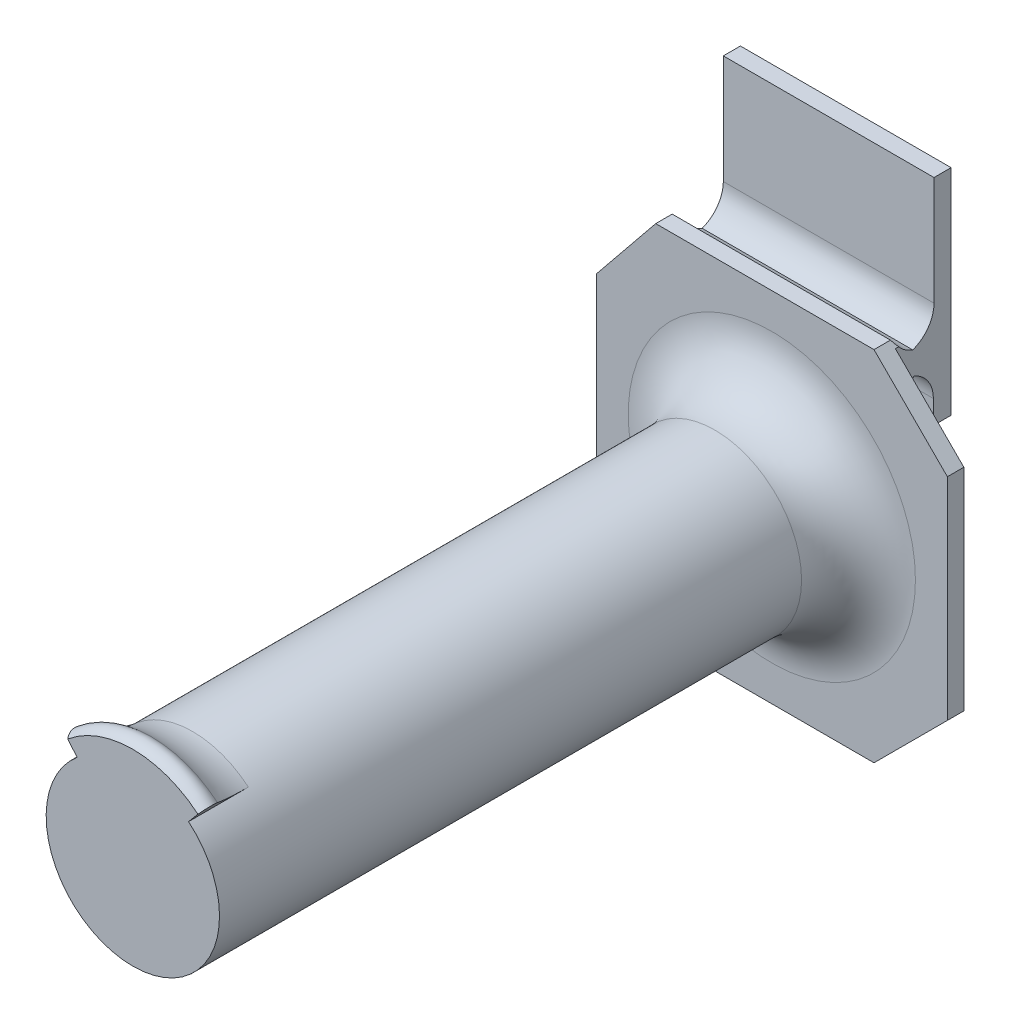
SolidWorks part; units mm, degrees
ref_plane "Front Plane" through (0, 0, 0) normal (0, 0, 1) x (1, 0, 0)
ref_plane "Top Plane" through (0, 0, 0) normal (0, 1, 0) x (1, 0, 0)
ref_plane "Right Plane" through (0, 0, 0) normal (1, 0, 0) x (0, 0, -1)
sketch "Sketch1" plane through (0, 0, 0) normal (0, 0, 1) x (1, 0, 0)
  circle A0 centre (0, 0) radius 13.7
extrude "Boss-Extrude1" add sketch "Sketch1" along normal blind 101
sketch "Sketch5" plane through (0, 0, 0) normal (0, 0, -1) x (-1, 0, 0)
  line L1 (27.75, 28.2807) -> (-27.75, 28.2807)
  line L2 (27.75, 28.2807) -> (27.75, -28.2807)
  line L3 (27.75, -28.2807) -> (-27.75, -28.2807)
  line L4 (-27.75, 28.2807) -> (-27.75, -28.2807)
  line L5 (27.75, 28.2807) -> (-27.75, -28.2807) construction
  line L6 (27.75, -28.2807) -> (-27.75, 28.2807) construction
  point P0 (0, 0)
extrude "Boss-Extrude2" add sketch "Sketch5" along normal blind 2.6 contours L1 L4 L3 L2
sketch "Sketch6" plane through (0, 0, -2.6) normal (0, 0, -1) x (-1, 0, 0)
  line L0 (-27.75, 16.6807) -> (-27.75, 28.2807)
  line L2 (27.75, 28.2807) -> (-27.75, 28.2807) construction
  line L3 (-16.15, 28.2807) -> (18.35, 28.2807) construction
  line L4 (-27.75, 0) -> (27.75, 0) construction
  line L5 (-27.75, 28.2807) -> (-27.75, -28.2807) construction
  line L6 (27.75, 28.2807) -> (27.75, -28.2807) construction
  line L7 (-16.15, -28.2807) -> (18.35, -28.2807)
  line L8 (-16.15, -28.2807) -> (-27.75, -16.6807)
  line L9 (-16.15, 28.2807) -> (-27.75, 16.6807)
  line L10 (1.1, -28.2807) -> (1.1, 28.2807) construction
  line L11 (18.35, -28.2807) -> (27.75, -18.8807)
  line L12 (27.75, -18.8807) -> (27.75, 16.6807)
  line L13 (27.75, 16.6807) -> (18.35, 28.2807)
  line L14 (-27.75, 16.6807) -> (-27.75, -16.6807) construction
  line L15 (-27.75, 28.2807) -> (-16.15, 28.2807)
  line L17 (18.35, 28.2807) -> (27.75, 28.2807)
  line L18 (27.75, 28.2807) -> (27.75, 16.6807)
  line L19 (27.75, -28.2807) -> (27.75, -18.8807)
  line L20 (18.35, -28.2807) -> (27.75, -28.2807)
  line L21 (-16.15, -28.2807) -> (-27.75, -28.2807)
  line L22 (-27.75, -28.2807) -> (-27.75, -16.6807)
  line M1 (27.75, -28.2807) -> (27.75, 28.2807)
  line M2 (27.75, 28.2807) -> (-27.75, 28.2807)
  line M3 (-27.75, 28.2807) -> (-27.75, -28.2807)
  line M4 (-27.75, -28.2807) -> (27.75, -28.2807)
extrude "Cut-Extrude4" cut sketch "Sketch6" against normal blind 2.6 contours L13 M1 M2 | L8 M4 M3 | L11 M4 M1 | L0 L15 L9 region at (23.8833, -24.414, -2.6) region at (-24.6167, 24.414, -2.6) region at (-24.6167, -25.1473, -2.6)
sketch "Sketch7" plane through (0, 0, -2.6) normal (0, 0, -1) x (-1, 0, 0)
  line L0 (1.1, 28.2807) -> (1.1, 25.6807) construction
  line L1 (18.35, 28.2807) -> (-16.15, 28.2807) construction
  line L2 (1.1, 25.6807) -> (16.3666, 25.6807)
  line L3 (16.3666, 25.6807) -> (16.3666, 22.6807)
  line L4 (-16.9334, 22.6807) -> (-16.9334, 25.6807)
  line L5 (16.3666, 22.6807) -> (-16.9334, 22.6807)
  line L6 (-16.9334, 25.6807) -> (1.1, 25.6807)
extrude "Boss-Extrude4" add sketch "Sketch7" along normal blind 6 contours L5 L4 L6 L2 L3
sketch "Sketch8" plane through (0, 0, -8.6) normal (0, 0, -1) x (-1, 0, 0)
  line L1 (-16.9334, 25.6807) -> (16.3666, 25.6807)
  line L2 (-16.9334, 25.6807) -> (-16.9334, 13.9807)
  line L3 (-16.9334, 13.9807) -> (16.3666, 13.9807)
  line L4 (16.3666, 25.6807) -> (16.3666, 13.9807)
  dimension "D1" = 11.7
extrude "Boss-Extrude5" add sketch "Sketch8" along normal blind 2.8
sketch "Sketch9" plane through (0, 25.6807, 0) normal (0, 1, 0) x (1, 0, 0)
  line L0 (16.9334, 11.4) -> (16.9334, 2.6) construction
  line L1 (-16.3666, 11.4) -> (16.9334, 11.4)
  line L2 (-16.3666, 11.4) -> (-16.3666, 8.7)
  line L3 (-16.3666, 8.7) -> (16.9334, 8.7)
  line L4 (16.9334, 11.4) -> (16.9334, 8.7)
  dimension "D1" = 2.7
extrude "Boss-Extrude6" add sketch "Sketch9" along normal blind 22.2
fillet "Fillet2" radius 5 4 edges at (0.2834, 25.6807, -2.6) (0.2834, 22.6807, -2.6) (0.2834, 25.6807, -8.7)
sketch3d "3DSketch3"
  circle A0 centre (0, 0, 101) radius 13.7 construction
  point P2 (0, 0, 114.7)
sketch "Sketch10" plane through (0, 0, 0) normal (-1, 0, 0) x (0, 0, 1)
  line L0 (101, -13.7) -> (101, 13.7) construction
  line L1 (101, -13.7) -> (101, 13.7) construction
  line L2 (101, 13.7) -> (101, 16)
  line L4 (101, 13.7) -> (91.5397, 13.7)
  arc A0 (101, 16) -> (98.0263, 16.2) centre (99.4136, 14.6199) ccw
  arc A1 (98.0263, 16.2) -> (91.5397, 13.7) centre (90.564, 25.8968) cw
sketch "Sketch11" plane through (0, 0, 0) normal (-1, 0, 0) x (0, 0, 1)
  line L0 (101.1008, 0) -> (0, 0) construction
revolve "Revolve1" add sketch "Sketch10" angle 40 about L0 other way angle 40
fillet "Fillet6" radius 9 1 edges at (13.7, 0, 0)
